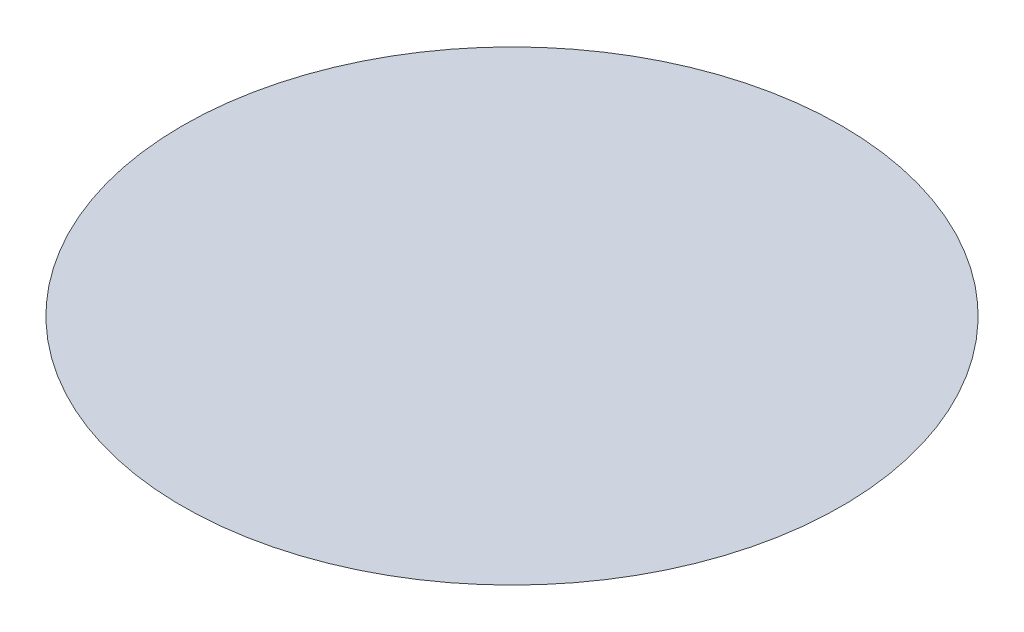
SolidWorks part; units mm, degrees
ref_plane "Front Plane" through (0, 0, 0) normal (0, 0, 1) x (1, 0, 0)
ref_plane "Top Plane" through (0, 0, 0) normal (0, 1, 0) x (1, 0, 0)
ref_plane "Right Plane" through (0, 0, 0) normal (1, 0, 0) x (0, 0, -1)
sketch "Sketch1" plane through (0, 0, 0) normal (0, 0, 1) x (1, 0, 0)
  line L0 (0, 0) -> (0, 28)
  line L1 (0, 28) -> (102.0657, 28)
  arc A0 (0, 0) -> (102.0657, 28) centre (0, 200.025) ccw
  point P5 (0, 0)
  dimension "D1" = 200.025
  dimension "D2" = 28
revolve "Revolve1" add sketch "Sketch1" angle 360 about L0
